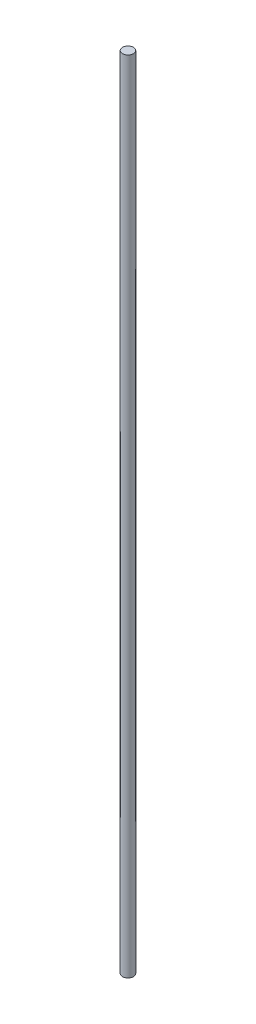
SolidWorks part; units mm, degrees
ref_plane "Front Plane" through (0, 0, 0) normal (0, 0, 1) x (1, 0, 0)
ref_plane "Top Plane" through (0, 0, 0) normal (0, 1, 0) x (1, 0, 0)
ref_plane "Right Plane" through (0, 0, 0) normal (1, 0, 0) x (0, 0, -1)
sketch "Sketch1" plane through (0, 0, 0) normal (0, 1, 0) x (1, 0, 0)
  circle A0 centre (0, 0) radius 1.397
  dimension "D1" = 2.794
extrude "Boss-Extrude1" add sketch "Sketch1" along normal blind 203.2
